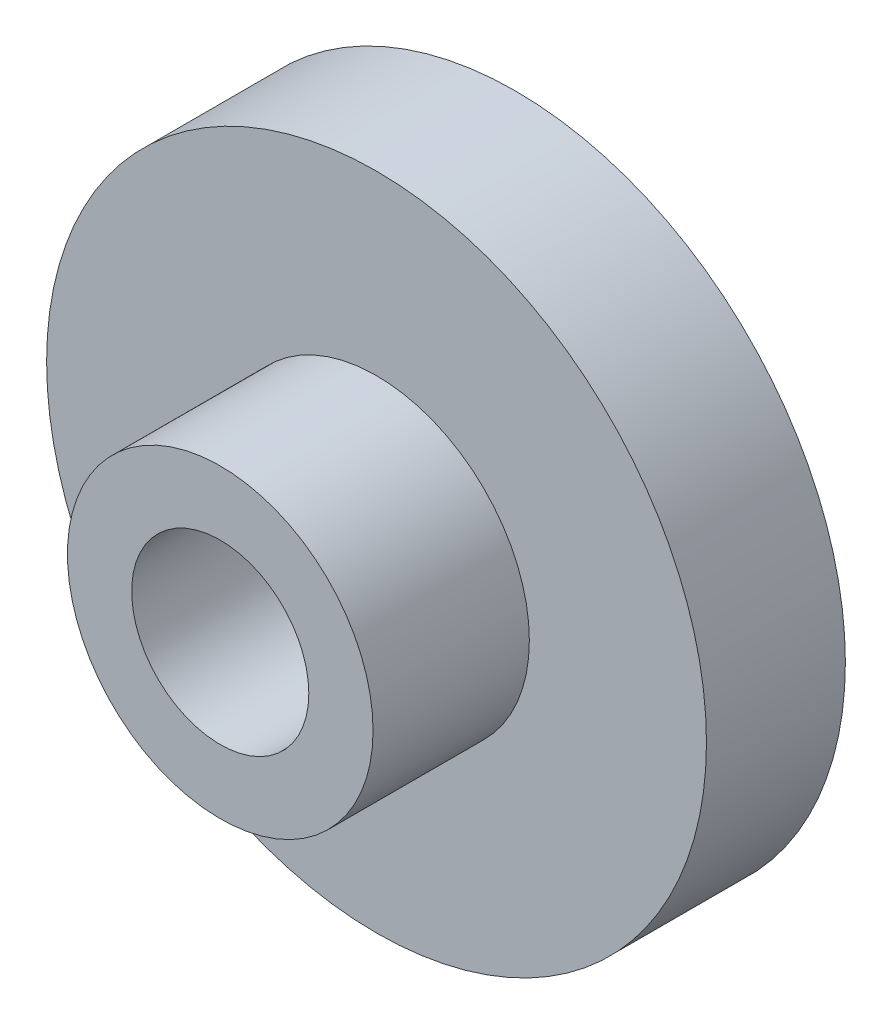
SolidWorks part; units mm, degrees
ref_plane "Front Plane" through (0, 0, 0) normal (0, 0, 1) x (1, 0, 0)
ref_plane "Top Plane" through (0, 0, 0) normal (0, 1, 0) x (1, 0, 0)
ref_plane "Right Plane" through (0, 0, 0) normal (1, 0, 0) x (0, 0, -1)
sketch "Sketch1" plane through (0, 0, 0) normal (0, 0, 1) x (1, 0, 0)
  circle A0 centre (0, 0) radius 4.75
  circle A1 centre (0, 0) radius 2.2
  circle A2 centre (0, 0) radius 1.275
  dimension "D1" = 9.5
  dimension "D2" = 4.4
  dimension "D3" = 2.55
extrude "Boss-Extrude1" add sketch "Sketch1" along normal blind 2 contours A0 A1 | A2 region at (-4.6156, 0, 0) region at (0, 0, 0)
extrude "Boss-Extrude2" add sketch "Sketch1<3>" along normal blind 4.25 contours A1 A2 region at (-2.1378, 0, 0)
sketch "Sketch1<3>" plane through (0, 0, 0) normal (0, 0, 1) x (1, 0, 0) same geometry as "Sketch1"
